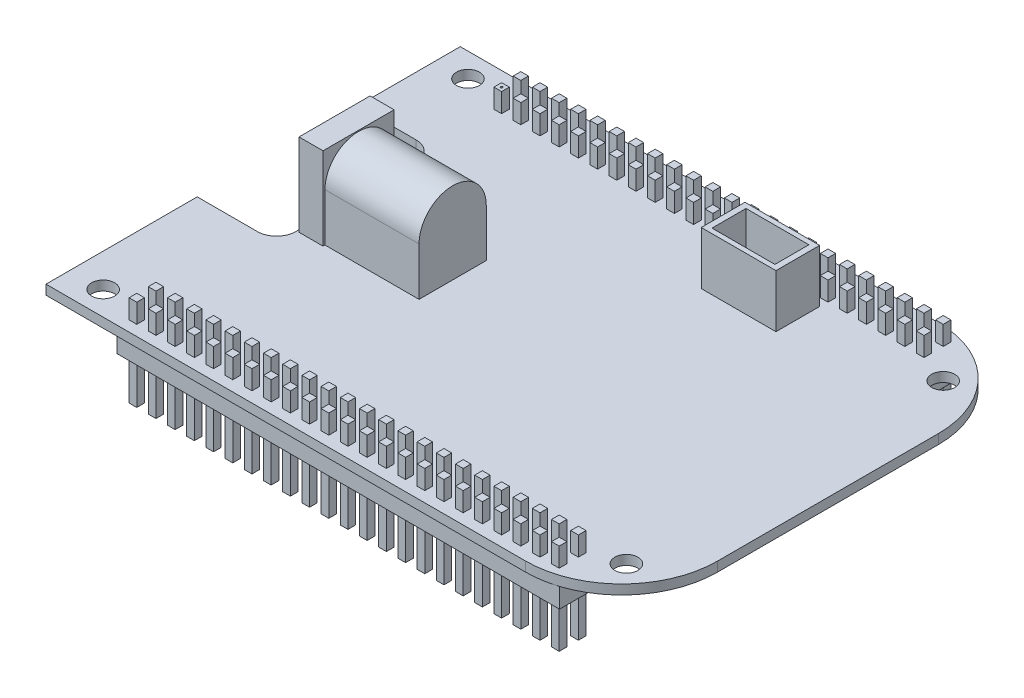
SolidWorks part; units mm, degrees
note: The reader was unsure of these and kept them because the rebuilt part matched: shared geometry of "Sketch10<3>".
material "cape"
ref_plane "Front Plane" through (0, 0, 0) normal (0, 0, 1) x (1, 0, 0)
ref_plane "Top Plane" through (0, 0, 0) normal (0, 1, 0) x (1, 0, 0)
ref_plane "Right Plane" through (0, 0, 0) normal (1, 0, 0) x (0, 0, -1)
sketch "Sketch1" plane through (0, 0, 0) normal (0, 1, 0) x (1, 0, 0)
  line L0 (-86.36, 27.305) -> (0, 27.305) construction
  line L1 (-12.7, 0) -> (-80.01, 0)
  line L2 (0, 12.7) -> (0, 41.91)
  line L3 (-12.7, 54.61) -> (-80.01, 54.61)
  line L4 (-86.36, 6.35) -> (-86.36, 48.26)
  line L5 (-71.755, 51.435) -> (-71.755, 3.175) construction
  line L6 (-5.715, 6.35) -> (-5.715, 48.26) construction
  arc A0 (0, 12.7) -> (-12.7, 0) centre (-12.7, 12.7) cw
  arc A1 (0, 41.91) -> (-12.7, 54.61) centre (-12.7, 41.91) ccw
  arc A2 (-86.36, 6.35) -> (-80.01, 0) centre (-80.01, 6.35) ccw
  arc A3 (-86.36, 48.26) -> (-80.01, 54.61) centre (-80.01, 48.26) cw
  circle A4 centre (-71.755, 51.435) radius 1.524
  circle A5 centre (-71.755, 3.175) radius 1.524
  circle A6 centre (-5.715, 6.35) radius 1.524
  circle A7 centre (-5.715, 48.26) radius 1.524
  point P7 (0, 0)
  point P10 (0, 54.61)
  point P13 (-86.36, 0)
  point P26 (-5.715, 27.305)
  point P27 (-71.755, 27.305)
  dimension "D3" = 12.7
  dimension "D4" = 6.35
  dimension "D6" = 41.91
  dimension "D9" = 3.048
  dimension "D1" = 86.36
  dimension "D2" = 54.61
  dimension "D5" = 48.26
  dimension "D7" = 5.715
  dimension "D8" = 14.605
extrude "Boss-Extrude1" add sketch "Sketch1" along normal blind 1.27
sketch "Sketch2" plane through (0, 1.27, 0) normal (0, 1, 0) x (1, 0, 0)
  line L0 (-80.01, 0) -> (-12.7, 0) construction
  line L1 (-5.715, 6.35) -> (-71.755, 6.35) construction
  line L3 (-86.36, 48.26) -> (-86.36, 6.35) construction
  line L4 (-5.715, 48.26) -> (-5.715, 6.35) construction
  circle A2 centre (-5.715, 48.26) radius 1.524
  circle A3 centre (-5.715, 6.35) radius 1.524
  dimension "D2" = 41.91
  dimension "D3" = 6.35
  dimension "D5" = 80.645
sketch "Sketch3" plane through (0, 1.27, 0) normal (0, 1, 0) x (1, 0, 0)
  line L0 (-10.16, 48.895) -> (-10.16, 50.165) construction
  line L1 (-67.31, 53.975) -> (-8.89, 53.975) construction
  line L2 (-67.31, 53.975) -> (-67.31, 48.895) construction
  line L3 (-67.31, 48.895) -> (-8.89, 48.895) construction
  line L4 (-8.89, 53.975) -> (-8.89, 48.895) construction
  line L5 (-86.36, 27.305) -> (0, 27.305) construction
  line L6 (0, 12.7) -> (0, 41.91) construction
  line L7 (-66.548, 4.953) -> (-66.548, 3.937)
  line L8 (-66.548, 4.953) -> (-65.532, 4.953)
  line L9 (-10.16, 50.165) -> (-10.16, 52.705) construction
  line L10 (-10.16, 52.705) -> (-10.16, 53.975) construction
  line L11 (-13.208, 52.197) -> (-12.192, 52.197)
  line L12 (-10.668, 53.213) -> (-9.652, 53.213)
  line L13 (-10.668, 53.213) -> (-10.668, 52.197)
  line L14 (-10.668, 52.197) -> (-9.652, 52.197)
  line L15 (-9.652, 53.213) -> (-9.652, 52.197)
  line L16 (-10.668, 53.213) -> (-9.652, 52.197) construction
  line L17 (-10.668, 52.197) -> (-9.652, 53.213) construction
  line L18 (-10.668, 49.657) -> (-9.652, 49.657)
  line L19 (-10.668, 49.657) -> (-10.668, 50.673)
  line L20 (-10.668, 50.673) -> (-9.652, 50.673)
  line L21 (-9.652, 49.657) -> (-9.652, 50.673)
  line L22 (-10.668, 49.657) -> (-9.652, 50.673) construction
  line L23 (-10.668, 50.673) -> (-9.652, 49.657) construction
  line L24 (-13.208, 53.213) -> (-13.208, 52.197)
  line L25 (-13.208, 53.213) -> (-12.192, 53.213)
  line L26 (-12.192, 53.213) -> (-12.192, 52.197)
  line L27 (-13.208, 50.673) -> (-12.192, 50.673)
  line L28 (-12.192, 49.657) -> (-12.192, 50.673)
  line L29 (-13.208, 49.657) -> (-12.192, 49.657)
  line L30 (-13.208, 49.657) -> (-13.208, 50.673)
  line L31 (-15.748, 52.197) -> (-14.732, 52.197)
  line L32 (-15.748, 53.213) -> (-15.748, 52.197)
  line L33 (-15.748, 53.213) -> (-14.732, 53.213)
  line L34 (-14.732, 53.213) -> (-14.732, 52.197)
  line L35 (-15.748, 50.673) -> (-14.732, 50.673)
  line L36 (-14.732, 49.657) -> (-14.732, 50.673)
  line L37 (-15.748, 49.657) -> (-14.732, 49.657)
  line L38 (-15.748, 49.657) -> (-15.748, 50.673)
  line L39 (-18.288, 52.197) -> (-17.272, 52.197)
  line L40 (-18.288, 53.213) -> (-18.288, 52.197)
  line L41 (-18.288, 53.213) -> (-17.272, 53.213)
  line L42 (-17.272, 53.213) -> (-17.272, 52.197)
  line L43 (-18.288, 50.673) -> (-17.272, 50.673)
  line L44 (-17.272, 49.657) -> (-17.272, 50.673)
  line L45 (-18.288, 49.657) -> (-17.272, 49.657)
  line L46 (-18.288, 49.657) -> (-18.288, 50.673)
  line L47 (-20.828, 52.197) -> (-19.812, 52.197)
  line L48 (-20.828, 53.213) -> (-20.828, 52.197)
  line L49 (-20.828, 53.213) -> (-19.812, 53.213)
  line L50 (-19.812, 53.213) -> (-19.812, 52.197)
  line L51 (-20.828, 50.673) -> (-19.812, 50.673)
  line L52 (-19.812, 49.657) -> (-19.812, 50.673)
  line L53 (-20.828, 49.657) -> (-19.812, 49.657)
  line L54 (-20.828, 49.657) -> (-20.828, 50.673)
  line L55 (-23.368, 52.197) -> (-22.352, 52.197)
  line L56 (-23.368, 53.213) -> (-23.368, 52.197)
  line L57 (-23.368, 53.213) -> (-22.352, 53.213)
  line L58 (-22.352, 53.213) -> (-22.352, 52.197)
  line L59 (-23.368, 50.673) -> (-22.352, 50.673)
  line L60 (-22.352, 49.657) -> (-22.352, 50.673)
  line L61 (-23.368, 49.657) -> (-22.352, 49.657)
  line L62 (-23.368, 49.657) -> (-23.368, 50.673)
  line L63 (-25.908, 52.197) -> (-24.892, 52.197)
  line L64 (-25.908, 53.213) -> (-25.908, 52.197)
  line L65 (-25.908, 53.213) -> (-24.892, 53.213)
  line L66 (-24.892, 53.213) -> (-24.892, 52.197)
  line L67 (-25.908, 50.673) -> (-24.892, 50.673)
  line L68 (-24.892, 49.657) -> (-24.892, 50.673)
  line L69 (-25.908, 49.657) -> (-24.892, 49.657)
  line L70 (-25.908, 49.657) -> (-25.908, 50.673)
  line L71 (-28.448, 52.197) -> (-27.432, 52.197)
  line L72 (-28.448, 53.213) -> (-28.448, 52.197)
  line L73 (-28.448, 53.213) -> (-27.432, 53.213)
  line L74 (-27.432, 53.213) -> (-27.432, 52.197)
  line L75 (-28.448, 50.673) -> (-27.432, 50.673)
  line L76 (-27.432, 49.657) -> (-27.432, 50.673)
  line L77 (-28.448, 49.657) -> (-27.432, 49.657)
  line L78 (-28.448, 49.657) -> (-28.448, 50.673)
  line L79 (-30.988, 52.197) -> (-29.972, 52.197)
  line L80 (-30.988, 53.213) -> (-30.988, 52.197)
  line L81 (-30.988, 53.213) -> (-29.972, 53.213)
  line L82 (-29.972, 53.213) -> (-29.972, 52.197)
  line L83 (-30.988, 50.673) -> (-29.972, 50.673)
  line L84 (-29.972, 49.657) -> (-29.972, 50.673)
  line L85 (-30.988, 49.657) -> (-29.972, 49.657)
  line L86 (-30.988, 49.657) -> (-30.988, 50.673)
  line L87 (-33.528, 52.197) -> (-32.512, 52.197)
  line L88 (-33.528, 53.213) -> (-33.528, 52.197)
  line L89 (-33.528, 53.213) -> (-32.512, 53.213)
  line L90 (-32.512, 53.213) -> (-32.512, 52.197)
  line L91 (-33.528, 50.673) -> (-32.512, 50.673)
  line L92 (-32.512, 49.657) -> (-32.512, 50.673)
  line L93 (-33.528, 49.657) -> (-32.512, 49.657)
  line L94 (-33.528, 49.657) -> (-33.528, 50.673)
  line L95 (-36.068, 52.197) -> (-35.052, 52.197)
  line L96 (-36.068, 53.213) -> (-36.068, 52.197)
  line L97 (-36.068, 53.213) -> (-35.052, 53.213)
  line L98 (-35.052, 53.213) -> (-35.052, 52.197)
  line L99 (-36.068, 50.673) -> (-35.052, 50.673)
  line L100 (-35.052, 49.657) -> (-35.052, 50.673)
  line L101 (-36.068, 49.657) -> (-35.052, 49.657)
  line L102 (-36.068, 49.657) -> (-36.068, 50.673)
  line L103 (-38.608, 52.197) -> (-37.592, 52.197)
  line L104 (-38.608, 53.213) -> (-38.608, 52.197)
  line L105 (-38.608, 53.213) -> (-37.592, 53.213)
  line L106 (-37.592, 53.213) -> (-37.592, 52.197)
  line L107 (-38.608, 50.673) -> (-37.592, 50.673)
  line L108 (-37.592, 49.657) -> (-37.592, 50.673)
  line L109 (-38.608, 49.657) -> (-37.592, 49.657)
  line L110 (-38.608, 49.657) -> (-38.608, 50.673)
  line L111 (-41.148, 52.197) -> (-40.132, 52.197)
  line L112 (-41.148, 53.213) -> (-41.148, 52.197)
  line L113 (-41.148, 53.213) -> (-40.132, 53.213)
  line L114 (-40.132, 53.213) -> (-40.132, 52.197)
  line L115 (-41.148, 50.673) -> (-40.132, 50.673)
  line L116 (-40.132, 49.657) -> (-40.132, 50.673)
  line L117 (-41.148, 49.657) -> (-40.132, 49.657)
  line L118 (-41.148, 49.657) -> (-41.148, 50.673)
  line L119 (-43.688, 52.197) -> (-42.672, 52.197)
  line L120 (-43.688, 53.213) -> (-43.688, 52.197)
  line L121 (-43.688, 53.213) -> (-42.672, 53.213)
  line L122 (-42.672, 53.213) -> (-42.672, 52.197)
  line L123 (-43.688, 50.673) -> (-42.672, 50.673)
  line L124 (-42.672, 49.657) -> (-42.672, 50.673)
  line L125 (-43.688, 49.657) -> (-42.672, 49.657)
  line L126 (-43.688, 49.657) -> (-43.688, 50.673)
  line L127 (-46.228, 52.197) -> (-45.212, 52.197)
  line L128 (-46.228, 53.213) -> (-46.228, 52.197)
  line L129 (-46.228, 53.213) -> (-45.212, 53.213)
  line L130 (-45.212, 53.213) -> (-45.212, 52.197)
  line L131 (-46.228, 50.673) -> (-45.212, 50.673)
  line L132 (-45.212, 49.657) -> (-45.212, 50.673)
  line L133 (-46.228, 49.657) -> (-45.212, 49.657)
  line L134 (-46.228, 49.657) -> (-46.228, 50.673)
  line L135 (-48.768, 52.197) -> (-47.752, 52.197)
  line L136 (-48.768, 53.213) -> (-48.768, 52.197)
  line L137 (-48.768, 53.213) -> (-47.752, 53.213)
  line L138 (-47.752, 53.213) -> (-47.752, 52.197)
  line L139 (-48.768, 50.673) -> (-47.752, 50.673)
  line L140 (-47.752, 49.657) -> (-47.752, 50.673)
  line L141 (-48.768, 49.657) -> (-47.752, 49.657)
  line L142 (-48.768, 49.657) -> (-48.768, 50.673)
  line L143 (-51.308, 52.197) -> (-50.292, 52.197)
  line L144 (-51.308, 53.213) -> (-51.308, 52.197)
  line L145 (-51.308, 53.213) -> (-50.292, 53.213)
  line L146 (-50.292, 53.213) -> (-50.292, 52.197)
  line L147 (-51.308, 50.673) -> (-50.292, 50.673)
  line L148 (-50.292, 49.657) -> (-50.292, 50.673)
  line L149 (-51.308, 49.657) -> (-50.292, 49.657)
  line L150 (-51.308, 49.657) -> (-51.308, 50.673)
  line L151 (-53.848, 52.197) -> (-52.832, 52.197)
  line L152 (-53.848, 53.213) -> (-53.848, 52.197)
  line L153 (-53.848, 53.213) -> (-52.832, 53.213)
  line L154 (-52.832, 53.213) -> (-52.832, 52.197)
  line L155 (-53.848, 50.673) -> (-52.832, 50.673)
  line L156 (-52.832, 49.657) -> (-52.832, 50.673)
  line L157 (-53.848, 49.657) -> (-52.832, 49.657)
  line L158 (-53.848, 49.657) -> (-53.848, 50.673)
  line L159 (-56.388, 52.197) -> (-55.372, 52.197)
  line L160 (-56.388, 53.213) -> (-56.388, 52.197)
  line L161 (-56.388, 53.213) -> (-55.372, 53.213)
  line L162 (-55.372, 53.213) -> (-55.372, 52.197)
  line L163 (-56.388, 50.673) -> (-55.372, 50.673)
  line L164 (-55.372, 49.657) -> (-55.372, 50.673)
  line L165 (-56.388, 49.657) -> (-55.372, 49.657)
  line L166 (-56.388, 49.657) -> (-56.388, 50.673)
  line L167 (-58.928, 52.197) -> (-57.912, 52.197)
  line L168 (-58.928, 53.213) -> (-58.928, 52.197)
  line L169 (-58.928, 53.213) -> (-57.912, 53.213)
  line L170 (-57.912, 53.213) -> (-57.912, 52.197)
  line L171 (-58.928, 50.673) -> (-57.912, 50.673)
  line L172 (-57.912, 49.657) -> (-57.912, 50.673)
  line L173 (-58.928, 49.657) -> (-57.912, 49.657)
  line L174 (-58.928, 49.657) -> (-58.928, 50.673)
  line L175 (-61.468, 52.197) -> (-60.452, 52.197)
  line L176 (-61.468, 53.213) -> (-61.468, 52.197)
  line L177 (-61.468, 53.213) -> (-60.452, 53.213)
  line L178 (-60.452, 53.213) -> (-60.452, 52.197)
  line L179 (-61.468, 50.673) -> (-60.452, 50.673)
  line L180 (-60.452, 49.657) -> (-60.452, 50.673)
  line L181 (-61.468, 49.657) -> (-60.452, 49.657)
  line L182 (-61.468, 49.657) -> (-61.468, 50.673)
  line L183 (-64.008, 52.197) -> (-62.992, 52.197)
  line L184 (-64.008, 53.213) -> (-64.008, 52.197)
  line L185 (-64.008, 53.213) -> (-62.992, 53.213)
  line L186 (-62.992, 53.213) -> (-62.992, 52.197)
  line L187 (-64.008, 50.673) -> (-62.992, 50.673)
  line L188 (-62.992, 49.657) -> (-62.992, 50.673)
  line L189 (-64.008, 49.657) -> (-62.992, 49.657)
  line L190 (-64.008, 49.657) -> (-64.008, 50.673)
  line L191 (-66.548, 52.197) -> (-65.532, 52.197)
  line L192 (-66.548, 53.213) -> (-66.548, 52.197)
  line L193 (-66.548, 53.213) -> (-65.532, 53.213)
  line L194 (-65.532, 53.213) -> (-65.532, 52.197)
  line L195 (-66.548, 50.673) -> (-65.532, 50.673)
  line L196 (-65.532, 49.657) -> (-65.532, 50.673)
  line L197 (-66.548, 49.657) -> (-65.532, 49.657)
  line L198 (-66.548, 49.657) -> (-66.548, 50.673)
  line L199 (-66.548, 49.657) -> (-65.532, 50.673) construction
  line L200 (-86.36, 48.26) -> (-86.36, 6.35) construction
  line L201 (-65.532, 4.953) -> (-65.532, 3.937)
  line L202 (-12.7, 54.61) -> (-80.01, 54.61) construction
  line L203 (-66.548, 3.937) -> (-65.532, 3.937)
  line L204 (-65.532, 1.397) -> (-65.532, 2.413)
  line L205 (-66.548, 1.397) -> (-65.532, 1.397)
  line L206 (-66.548, 1.397) -> (-66.548, 2.413)
  line L207 (-66.548, 2.413) -> (-65.532, 2.413)
  line L208 (-64.008, 4.953) -> (-64.008, 3.937)
  line L209 (-64.008, 4.953) -> (-62.992, 4.953)
  line L210 (-62.992, 4.953) -> (-62.992, 3.937)
  line L211 (-64.008, 3.937) -> (-62.992, 3.937)
  line L212 (-62.992, 1.397) -> (-62.992, 2.413)
  line L213 (-64.008, 1.397) -> (-62.992, 1.397)
  line L214 (-64.008, 1.397) -> (-64.008, 2.413)
  line L215 (-64.008, 2.413) -> (-62.992, 2.413)
  line L216 (-61.468, 4.953) -> (-61.468, 3.937)
  line L217 (-61.468, 4.953) -> (-60.452, 4.953)
  line L218 (-60.452, 4.953) -> (-60.452, 3.937)
  line L219 (-61.468, 3.937) -> (-60.452, 3.937)
  line L220 (-60.452, 1.397) -> (-60.452, 2.413)
  line L221 (-61.468, 1.397) -> (-60.452, 1.397)
  line L222 (-61.468, 1.397) -> (-61.468, 2.413)
  line L223 (-61.468, 2.413) -> (-60.452, 2.413)
  line L224 (-58.928, 4.953) -> (-58.928, 3.937)
  line L225 (-58.928, 4.953) -> (-57.912, 4.953)
  line L226 (-57.912, 4.953) -> (-57.912, 3.937)
  line L227 (-58.928, 3.937) -> (-57.912, 3.937)
  line L228 (-57.912, 1.397) -> (-57.912, 2.413)
  line L229 (-58.928, 1.397) -> (-57.912, 1.397)
  line L230 (-58.928, 1.397) -> (-58.928, 2.413)
  line L231 (-58.928, 2.413) -> (-57.912, 2.413)
  line L232 (-56.388, 4.953) -> (-56.388, 3.937)
  line L233 (-56.388, 4.953) -> (-55.372, 4.953)
  line L234 (-55.372, 4.953) -> (-55.372, 3.937)
  line L235 (-56.388, 3.937) -> (-55.372, 3.937)
  line L236 (-55.372, 1.397) -> (-55.372, 2.413)
  line L237 (-56.388, 1.397) -> (-55.372, 1.397)
  line L238 (-56.388, 1.397) -> (-56.388, 2.413)
  line L239 (-56.388, 2.413) -> (-55.372, 2.413)
  line L240 (-53.848, 4.953) -> (-53.848, 3.937)
  line L241 (-53.848, 4.953) -> (-52.832, 4.953)
  line L242 (-52.832, 4.953) -> (-52.832, 3.937)
  line L243 (-53.848, 3.937) -> (-52.832, 3.937)
  line L244 (-52.832, 1.397) -> (-52.832, 2.413)
  line L245 (-53.848, 1.397) -> (-52.832, 1.397)
  line L246 (-53.848, 1.397) -> (-53.848, 2.413)
  line L247 (-53.848, 2.413) -> (-52.832, 2.413)
  line L248 (-51.308, 4.953) -> (-51.308, 3.937)
  line L249 (-51.308, 4.953) -> (-50.292, 4.953)
  line L250 (-50.292, 4.953) -> (-50.292, 3.937)
  line L251 (-51.308, 3.937) -> (-50.292, 3.937)
  line L252 (-50.292, 1.397) -> (-50.292, 2.413)
  line L253 (-51.308, 1.397) -> (-50.292, 1.397)
  line L254 (-51.308, 1.397) -> (-51.308, 2.413)
  line L255 (-51.308, 2.413) -> (-50.292, 2.413)
  line L256 (-48.768, 4.953) -> (-48.768, 3.937)
  line L257 (-48.768, 4.953) -> (-47.752, 4.953)
  line L258 (-47.752, 4.953) -> (-47.752, 3.937)
  line L259 (-48.768, 3.937) -> (-47.752, 3.937)
  line L260 (-47.752, 1.397) -> (-47.752, 2.413)
  line L261 (-48.768, 1.397) -> (-47.752, 1.397)
  line L262 (-48.768, 1.397) -> (-48.768, 2.413)
  line L263 (-48.768, 2.413) -> (-47.752, 2.413)
  line L264 (-46.228, 4.953) -> (-46.228, 3.937)
  line L265 (-46.228, 4.953) -> (-45.212, 4.953)
  line L266 (-45.212, 4.953) -> (-45.212, 3.937)
  line L267 (-46.228, 3.937) -> (-45.212, 3.937)
  line L268 (-45.212, 1.397) -> (-45.212, 2.413)
  line L269 (-46.228, 1.397) -> (-45.212, 1.397)
  line L270 (-46.228, 1.397) -> (-46.228, 2.413)
  line L271 (-46.228, 2.413) -> (-45.212, 2.413)
  line L272 (-43.688, 4.953) -> (-43.688, 3.937)
  line L273 (-43.688, 4.953) -> (-42.672, 4.953)
  line L274 (-42.672, 4.953) -> (-42.672, 3.937)
  line L275 (-43.688, 3.937) -> (-42.672, 3.937)
  line L276 (-42.672, 1.397) -> (-42.672, 2.413)
  line L277 (-43.688, 1.397) -> (-42.672, 1.397)
  line L278 (-43.688, 1.397) -> (-43.688, 2.413)
  line L279 (-43.688, 2.413) -> (-42.672, 2.413)
  line L280 (-41.148, 4.953) -> (-41.148, 3.937)
  line L281 (-41.148, 4.953) -> (-40.132, 4.953)
  line L282 (-40.132, 4.953) -> (-40.132, 3.937)
  line L283 (-41.148, 3.937) -> (-40.132, 3.937)
  line L284 (-40.132, 1.397) -> (-40.132, 2.413)
  line L285 (-41.148, 1.397) -> (-40.132, 1.397)
  line L286 (-41.148, 1.397) -> (-41.148, 2.413)
  line L287 (-41.148, 2.413) -> (-40.132, 2.413)
  line L288 (-38.608, 4.953) -> (-38.608, 3.937)
  line L289 (-38.608, 4.953) -> (-37.592, 4.953)
  line L290 (-37.592, 4.953) -> (-37.592, 3.937)
  line L291 (-38.608, 3.937) -> (-37.592, 3.937)
  line L292 (-37.592, 1.397) -> (-37.592, 2.413)
  line L293 (-38.608, 1.397) -> (-37.592, 1.397)
  line L294 (-38.608, 1.397) -> (-38.608, 2.413)
  line L295 (-38.608, 2.413) -> (-37.592, 2.413)
  line L296 (-36.068, 4.953) -> (-36.068, 3.937)
  line L297 (-36.068, 4.953) -> (-35.052, 4.953)
  line L298 (-35.052, 4.953) -> (-35.052, 3.937)
  line L299 (-36.068, 3.937) -> (-35.052, 3.937)
  line L300 (-35.052, 1.397) -> (-35.052, 2.413)
  line L301 (-36.068, 1.397) -> (-35.052, 1.397)
  line L302 (-36.068, 1.397) -> (-36.068, 2.413)
  line L303 (-36.068, 2.413) -> (-35.052, 2.413)
  line L304 (-33.528, 4.953) -> (-33.528, 3.937)
  line L305 (-33.528, 4.953) -> (-32.512, 4.953)
  line L306 (-32.512, 4.953) -> (-32.512, 3.937)
  line L307 (-33.528, 3.937) -> (-32.512, 3.937)
  line L308 (-32.512, 1.397) -> (-32.512, 2.413)
  line L309 (-33.528, 1.397) -> (-32.512, 1.397)
  line L310 (-33.528, 1.397) -> (-33.528, 2.413)
  line L311 (-33.528, 2.413) -> (-32.512, 2.413)
  line L312 (-30.988, 4.953) -> (-30.988, 3.937)
  line L313 (-30.988, 4.953) -> (-29.972, 4.953)
  line L314 (-29.972, 4.953) -> (-29.972, 3.937)
  line L315 (-30.988, 3.937) -> (-29.972, 3.937)
  line L316 (-29.972, 1.397) -> (-29.972, 2.413)
  line L317 (-30.988, 1.397) -> (-29.972, 1.397)
  line L318 (-30.988, 1.397) -> (-30.988, 2.413)
  line L319 (-30.988, 2.413) -> (-29.972, 2.413)
  line L320 (-28.448, 4.953) -> (-28.448, 3.937)
  line L321 (-28.448, 4.953) -> (-27.432, 4.953)
  line L322 (-27.432, 4.953) -> (-27.432, 3.937)
  line L323 (-28.448, 3.937) -> (-27.432, 3.937)
  line L324 (-27.432, 1.397) -> (-27.432, 2.413)
  line L325 (-28.448, 1.397) -> (-27.432, 1.397)
  line L326 (-28.448, 1.397) -> (-28.448, 2.413)
  line L327 (-28.448, 2.413) -> (-27.432, 2.413)
  line L328 (-25.908, 4.953) -> (-25.908, 3.937)
  line L329 (-25.908, 4.953) -> (-24.892, 4.953)
  line L330 (-24.892, 4.953) -> (-24.892, 3.937)
  line L331 (-25.908, 3.937) -> (-24.892, 3.937)
  line L332 (-24.892, 1.397) -> (-24.892, 2.413)
  line L333 (-25.908, 1.397) -> (-24.892, 1.397)
  line L334 (-25.908, 1.397) -> (-25.908, 2.413)
  line L335 (-25.908, 2.413) -> (-24.892, 2.413)
  line L336 (-23.368, 4.953) -> (-23.368, 3.937)
  line L337 (-23.368, 4.953) -> (-22.352, 4.953)
  line L338 (-22.352, 4.953) -> (-22.352, 3.937)
  line L339 (-23.368, 3.937) -> (-22.352, 3.937)
  line L340 (-22.352, 1.397) -> (-22.352, 2.413)
  line L341 (-23.368, 1.397) -> (-22.352, 1.397)
  line L342 (-23.368, 1.397) -> (-23.368, 2.413)
  line L343 (-23.368, 2.413) -> (-22.352, 2.413)
  line L344 (-20.828, 4.953) -> (-20.828, 3.937)
  line L345 (-20.828, 4.953) -> (-19.812, 4.953)
  line L346 (-19.812, 4.953) -> (-19.812, 3.937)
  line L347 (-20.828, 3.937) -> (-19.812, 3.937)
  line L348 (-19.812, 1.397) -> (-19.812, 2.413)
  line L349 (-20.828, 1.397) -> (-19.812, 1.397)
  line L350 (-20.828, 1.397) -> (-20.828, 2.413)
  line L351 (-20.828, 2.413) -> (-19.812, 2.413)
  line L352 (-18.288, 4.953) -> (-18.288, 3.937)
  line L353 (-18.288, 4.953) -> (-17.272, 4.953)
  line L354 (-17.272, 4.953) -> (-17.272, 3.937)
  line L355 (-18.288, 3.937) -> (-17.272, 3.937)
  line L356 (-17.272, 1.397) -> (-17.272, 2.413)
  line L357 (-18.288, 1.397) -> (-17.272, 1.397)
  line L358 (-18.288, 1.397) -> (-18.288, 2.413)
  line L359 (-18.288, 2.413) -> (-17.272, 2.413)
  line L360 (-15.748, 4.953) -> (-15.748, 3.937)
  line L361 (-15.748, 4.953) -> (-14.732, 4.953)
  line L362 (-14.732, 4.953) -> (-14.732, 3.937)
  line L363 (-15.748, 3.937) -> (-14.732, 3.937)
  line L364 (-14.732, 1.397) -> (-14.732, 2.413)
  line L365 (-15.748, 1.397) -> (-14.732, 1.397)
  line L366 (-15.748, 1.397) -> (-15.748, 2.413)
  line L367 (-15.748, 2.413) -> (-14.732, 2.413)
  line L368 (-13.208, 4.953) -> (-13.208, 3.937)
  line L369 (-13.208, 4.953) -> (-12.192, 4.953)
  line L370 (-12.192, 4.953) -> (-12.192, 3.937)
  line L371 (-13.208, 3.937) -> (-12.192, 3.937)
  line L372 (-12.192, 1.397) -> (-12.192, 2.413)
  line L373 (-13.208, 1.397) -> (-12.192, 1.397)
  line L374 (-13.208, 1.397) -> (-13.208, 2.413)
  line L375 (-9.652, 4.953) -> (-9.652, 3.937)
  line L376 (-10.668, 3.937) -> (-9.652, 3.937)
  line L377 (-10.668, 4.953) -> (-10.668, 3.937)
  line L378 (-10.668, 4.953) -> (-9.652, 4.953)
  line L379 (-9.652, 1.397) -> (-9.652, 2.413)
  line L380 (-10.668, 2.413) -> (-9.652, 2.413)
  line L381 (-10.668, 1.397) -> (-10.668, 2.413)
  line L382 (-10.668, 1.397) -> (-9.652, 1.397)
  line L383 (-13.208, 2.413) -> (-12.192, 2.413)
  line L384 (-8.89, 0.635) -> (-8.89, 5.715) construction
  line L385 (-67.31, 5.715) -> (-8.89, 5.715) construction
  line L386 (-67.31, 0.635) -> (-67.31, 5.715) construction
  line L387 (-67.31, 0.635) -> (-8.89, 0.635) construction
  circle A0 centre (-66.04, 50.165) radius 0.1361
  dimension "D1" = 1.016
  dimension "D2" = 2.54
  dimension "D3" = 5.08
  dimension "D4" = 58.42
  dimension "D5" = 1.27
  dimension "D7" = 20.32
  dimension "D8" = 0.635
  dimension "D6" = 23
extrude "Boss-Extrude2" add sketch "Sketch3" along normal blind 2.54 and the other way blind 9.525
sketch "Sketch14" plane through (0, 1.27, 0) normal (0, 1, 0) x (1, 0, 0)
  line L0 (-75.9484, 54.61) -> (-75.9484, 41.0079)
  line L1 (-12.7, 54.61) -> (-80.01, 54.61) construction
  line L2 (-65.6397, 38.4679) -> (-65.6397, 22.5426)
  line L3 (-76.1396, 20.0026) -> (-76.1396, 0)
  line L4 (-80.01, 0) -> (-12.7, 0) construction
  line L5 (-75.9484, 54.61) -> (-105.3672, 54.61)
  line L6 (-105.3672, 54.61) -> (-105.3672, 0)
  line L7 (-105.3672, 0) -> (-76.1396, 0)
  line L8 (0, 12.7) -> (0, 41.91) construction
  line L9 (-75.9484, 41.0079) -> (-68.1797, 41.0079)
  line L10 (-76.1396, 20.0026) -> (-68.1797, 20.0026)
  arc A0 (-68.1797, 41.0079) -> (-65.6397, 38.4679) centre (-68.1797, 38.4679) cw
  arc A1 (-68.1797, 20.0026) -> (-65.6397, 22.5426) centre (-68.1797, 22.5426) ccw
  dimension "D1" = 75.9484
  dimension "D2" = 2.54
  dimension "D3" = 76.1396
  dimension "D4" = 65.6397
  dimension "D5" = 13.6021
  dimension "D6" = 20.0026
extrude "Cut-Extrude5" cut sketch "Sketch14" against normal through all
sketch "Sketch9" plane through (0, 1.27, 0) normal (0, 1, 0) x (1, 0, 0)
  line L1 (-49.7208, 22.9284) -> (-65.3418, 22.9284)
  line L2 (-49.7208, 22.9284) -> (-49.7208, 31.8184)
  line L3 (-49.7208, 31.8184) -> (-65.3418, 31.8184)
  line L4 (-65.3418, 22.9284) -> (-65.3418, 31.8184)
  dimension "D1" = 8.89
  dimension "D2" = 15.621
extrude "Boss-Extrude6" add sketch "Sketch9" along normal blind 6.35
sketch "Sketch10" plane through (-65.3418, 0, 0) normal (-1, 0, 0) x (0, 0, 1)
  line L0 (-31.8184, 7.62) -> (-22.9284, 7.62) construction
  circle A0 centre (-27.3734, 7.62) radius 4.445
  circle A1 centre (-27.3734, 7.62) radius 3.4925
  circle A2 centre (-27.3734, 7.62) radius 0.635
  line M3 (-22.9284, 7.62) -> (-31.8184, 7.62)
  dimension "D1" = 1.27
  dimension "D2" = 6.985
extrude "Boss-Extrude7" add sketch "Sketch10" along direction (1, 0, 0) on the side against the normal up to surface (15.621 mm away) contours A1 A0 M3 | A1 A0 M3 | A2 M3 | A2 A1 M3 up to face at (-49.7208, 4.445, -27.3734)
sketch "Sketch11" plane through (-65.3418, 0, 0) normal (-1, 0, 0) x (0, 0, 1)
  line L0 (-31.8184, 7.62) -> (-31.8184, 1.27) construction
  line L1 (-22.6744, 1.27) -> (-32.0724, 1.27)
  line L2 (-22.6744, 1.27) -> (-22.6744, 12.1969)
  line L3 (-22.6744, 12.1969) -> (-32.0724, 12.1969)
  line L4 (-32.0724, 1.27) -> (-32.0724, 12.1969)
  line L5 (-22.6744, 1.27) -> (-32.0724, 12.1969) construction
  line L6 (-22.6744, 12.1969) -> (-32.0724, 1.27) construction
  line L7 (-22.5426, 1.27) -> (-38.4679, 1.27) construction
  arc A0 (-22.9284, 7.62) -> (-31.8184, 7.62) centre (-27.3734, 7.62) ccw construction
  point P0 (-27.3734, 6.7335)
  point P8 (-27.3734, 7.62)
  point P11 (-27.3734, 12.065)
  dimension "D1" = 0.254
  dimension "D2" = 0.1319
extrude "Boss-Extrude8" add sketch "Sketch11" against normal blind 3.175
extrude "Cut-Extrude4" cut sketch "Sketch10<3>" against normal blind 12.7 contours A2 A1 M3 | A2 A1 M3
sketch "Sketch10<3>" plane through (-65.3418, 0, 0) normal (-1, 0, 0) x (0, 0, 1) same geometry as "Sketch10"
fillet "Fillet1" radius 0.635 1 edges at (-65.3418, 7.62, -26.7384)
ref_plane "Vertical Plane" through (0, 0, -27.305) normal (0, 0, 1) x (1, 0, 0)
ref_plane "Plane1" through (0, 1.27, 0) normal (0, 1, 0) x (1, 0, 0)
sketch "Sketch16" plane through (0, 0, 0) normal (0, -1, 0) x (1, 0, 0)
  line L0 (-1000, -27.305) -> (49000, -27.305) construction
  line L1 (-67.3219, -0.5423) -> (-8.7493, -0.5423)
  line L2 (-67.3219, -0.5423) -> (-67.3219, -5.897)
  line L3 (-67.3219, -5.897) -> (-8.7493, -5.897)
  line L4 (-8.7493, -0.5423) -> (-8.7493, -5.897)
  line L5 (0, -12.7) -> (0, -41.91) construction
  line L6 (-8.7493, -54.0677) -> (-8.7493, -48.713)
  line L7 (-67.3219, -48.713) -> (-8.7493, -48.713)
  line L8 (-67.3219, -54.0677) -> (-67.3219, -48.713)
  line L9 (-67.3219, -54.0677) -> (-8.7493, -54.0677)
  point P9 (0, -27.305)
extrude "Boss-Extrude9" add sketch "Sketch16" along normal blind 2.54
sketch "Sketch17" plane through (0, 1.27, 0) normal (0, 1, 0) x (1, 0, 0)
  line L0 (-12.7, 54.61) -> (-75.9484, 54.61) construction
  line L1 (-32.29, 42.83) -> (-22.41, 42.83)
  line L2 (-32.29, 42.83) -> (-32.29, 48.61)
  line L3 (-32.29, 48.61) -> (-22.41, 48.61)
  line L4 (-22.41, 42.83) -> (-22.41, 48.61)
  line L5 (-32.29, 42.83) -> (-22.41, 48.61) construction
  line L6 (-32.29, 48.61) -> (-22.41, 42.83) construction
  line L7 (-31.51, 43.47) -> (-23.19, 43.47)
  line L8 (-31.51, 43.47) -> (-31.51, 47.97)
  line L9 (-31.51, 47.97) -> (-23.19, 47.97)
  line L10 (-23.19, 43.47) -> (-23.19, 47.97)
  line L11 (-31.51, 43.47) -> (-23.19, 47.97) construction
  line L12 (-31.51, 47.97) -> (-23.19, 43.47) construction
  line L13 (0, 12.7) -> (0, 41.91) construction
  point P0 (-27.35, 45.72)
  point P5 (-27.35, 45.72)
  dimension "D1" = 0.64
  dimension "D2" = 0.78
  dimension "D3" = 6
  dimension "D4" = 22.41
  dimension "D5" = 9.88
  dimension "D6" = 5.78
extrude "Boss-Extrude10" add sketch "Sketch17" along normal blind 7
